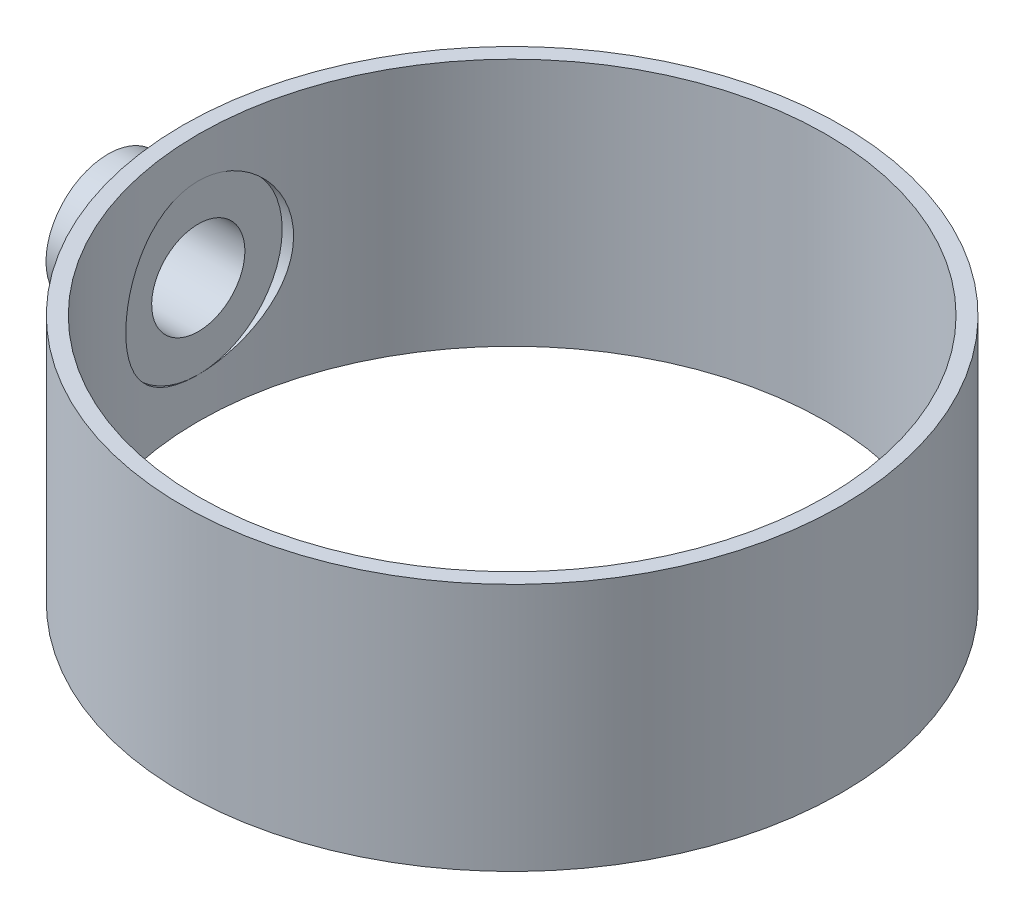
SolidWorks part; units mm, degrees
ref_plane "前视基准面" through (0, 0, 0) normal (0, 0, 1) x (1, 0, 0)
ref_plane "上视基准面" through (0, 0, 0) normal (0, 1, 0) x (1, 0, 0)
ref_plane "右视基准面" through (0, 0, 0) normal (1, 0, 0) x (0, 0, -1)
sketch "草图1" plane through (0, 0, 0) normal (0, 1, 0) x (1, 0, 0)
  circle A0 centre (0, 0) radius 101
  dimension "D1" = 202
extrude "拉伸-薄壁1" add sketch "草图1" along normal mid plane 80 thin thin type one direction wall 5
sketch "草图2" plane through (0, 0, 0) normal (1, 0, 0) x (0, 0, -1)
  circle A0 centre (0, 0) radius 15
  dimension "D1" = 30
extrude "切除-拉伸1" cut sketch "草图2" against normal up to next
sketch "草图3" plane through (0, 0, 0) normal (1, 0, 0) x (0, 0, -1)
  circle A0 centre (0, 0) radius 20
  circle A1 centre (0, 0) radius 15 construction
  circle A2 centre (0, 0) radius 15
  dimension "D1" = 40
extrude "凸台-拉伸1" add sketch "草图3" along normal up to next from offset 130 offset against normal yes
sketch "草图4" plane through (-130, 0, 0) normal (-1, 0, 0) x (0, 0, 1)
  circle A0 centre (0, 0) radius 17.5 construction
  point P3 (17.5, 0)
  point P7 (0, -17.5)
  point P8 (-17.5, 0)
  point P9 (0, 17.5)
  dimension "D1" = 35
  dimension "D2" = 4
hole_wizard "M3 螺纹孔1" positions "草图4" profile "草图6" tap size "M3" standard "GB"
sketch "草图6" plane through (-130, 17.5, 0) normal (0, 1, 0) x (0, 0, 1)
  line L0 (0, 0) -> (0, 15.7511)
  line L1 (0, 15.7511) -> (1.25, 15)
  line L2 (1.25, 15) -> (1.25, 0)
  line L5 (1.25, 0) -> (0, 0)
  line L10 (0, 15.7511) -> (-1.25, 15) construction
  line L11 (0, -6.35) -> (0, 107.95) construction
  dimension "螺纹孔钻头直径" = 2.5
  dimension "螺纹孔钻头深度" = 15
  dimension "导头角度" = 118
cosmetic thread "孔螺纹线1" parameters "D1"=15, "D2"=3
cosmetic thread "孔螺纹线2" parameters "D1"=15, "D2"=3
cosmetic thread "孔螺纹线3" parameters "D1"=15, "D2"=3
cosmetic thread "孔螺纹线4" parameters "D1"=15, "D2"=3
fillet "圆角1" radius 10 1 edges at (-104.181, -4.2053, -19.5529)
sketch "草图7" plane through (-130, 0, 0) normal (-1, 0, 0) x (0, 0, 1)
  circle A0 centre (0, 0) radius 24
  dimension "D1" = 48
sketch "草图9" plane through (0, 0, 0) normal (0, 0, 1) x (1, 0, 0)
  line L0 (-101, 0) -> (-101, 27)
  line L1 (116.6, 0) -> (-116.6, 0) construction
  line L2 (-101, 27) -> (-77.8565, 27)
  line L3 (-77.8565, 27) -> (-77.8565, 0)
  line L4 (-77.8565, 0) -> (-101, 0) construction
  line L5 (-130, 24) -> (-130, -24) construction
  line L6 (-101, 0) -> (-77.8565, 0)
  dimension "D1" = 29
  dimension "D2" = 54
revolve "切除-旋转1" cut sketch "草图9" angle 360 about L4
